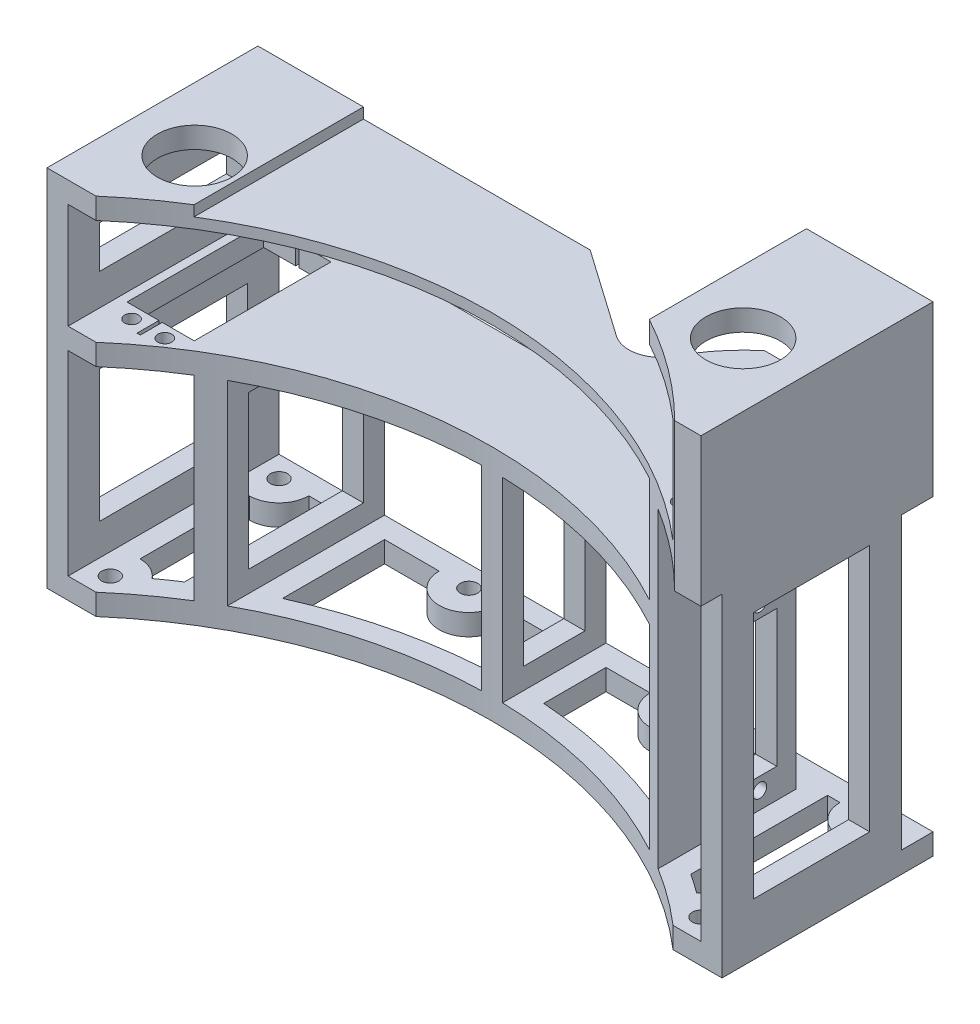
SolidWorks part; units mm, degrees
ref_plane "Front Plane" through (0, 0, 0) normal (0, 0, 1) x (1, 0, 0)
ref_plane "Top Plane" through (0, 0, 0) normal (0, 1, 0) x (1, 0, 0)
ref_plane "Right Plane" through (0, 0, 0) normal (1, 0, 0) x (0, 0, -1)
sketch "Sketch1" plane through (0, 0, 0) normal (0, 0, 1) x (1, 0, 0)
  line L0 (-101.6, 106.425) -> (101.6, 106.425)
  line L1 (-101.6, 0) -> (101.6, 0)
  line L2 (-101.6, 0) -> (-101.6, 106.425)
  line L4 (101.6, 0) -> (101.6, 106.425)
  point P5 (0, 0)
  dimension "D1" = 203.2
  dimension "D2" = 106.425
extrude "Boss-Extrude1" add sketch "Sketch1" along normal mid plane 63.5 contours L1 L4 L0 L2 | L0 region at (0, 53.2125, 0)
sketch "Sketch4" plane through (0, 0, -31.75) normal (0, 0, -1) x (-1, 0, 0)
  line L0 (-101.6, 0) -> (-101.6, 106.425) construction
  line L1 (101.6, 0) -> (101.6, 106.425) construction
  line L2 (-95.25, 103.25) -> (95.25, 103.25)
  line L3 (-95.25, 103.25) -> (-95.25, 71.5)
  line L4 (-95.25, 71.5) -> (95.25, 71.5)
  line L5 (95.25, 103.25) -> (95.25, 71.5)
  line L11 (-95.25, 65.15) -> (95.25, 65.15)
  line L12 (-95.25, 65.15) -> (-95.25, 6.35)
  line L13 (-95.25, 6.35) -> (95.25, 6.35)
  line L14 (95.25, 65.15) -> (95.25, 6.35)
  line L15 (101.6, 0) -> (-101.6, 0) construction
  dimension "D4" = 6.35
  dimension "D1" = 6.35
  dimension "D2" = 71.5
  dimension "D3" = 6.35
  dimension "D5" = 6.35
  dimension "D6" = 31.75
extrude "Cut-Extrude2" cut sketch "Sketch4" against normal through all
sketch "Sketch8" plane through (0, 0, 0) normal (0, 0, 1) x (1, 0, 0)
  line L0 (-95.25, 65.15) -> (95.25, 65.15) construction
  line L1 (-69.85, 65.15) -> (-63.5, 65.15)
  line L2 (-69.85, 65.15) -> (-69.85, 6.35)
  line L3 (-69.85, 6.35) -> (-63.5, 6.35)
  line L4 (-63.5, 65.15) -> (-63.5, 6.35)
  line L5 (95.25, 6.35) -> (-95.25, 6.35) construction
  line L6 (-95.25, 103.25) -> (95.25, 103.25) construction
  line L7 (63.5, 103.25) -> (69.85, 103.25)
  line L8 (63.5, 103.25) -> (63.5, 6.35)
  line L9 (63.5, 6.35) -> (69.85, 6.35)
  line L10 (69.85, 103.25) -> (69.85, 6.35)
  line L11 (95.25, 65.15) -> (95.25, 6.35) construction
  line L12 (-95.25, 6.35) -> (-95.25, 65.15) construction
  line L13 (-101.6, 0) -> (101.6, 0) construction
  line L14 (-3.175, 65.15) -> (3.175, 65.15)
  line L15 (-3.175, 65.15) -> (-3.175, 6.35)
  line L16 (-3.175, 6.35) -> (3.175, 6.35)
  line L17 (3.175, 65.15) -> (3.175, 6.35)
  point P24 (0, 0)
  point P25 (0, 6.35)
  dimension "D1" = 6.35
  dimension "D2" = 6.35
  dimension "D3" = 25.4
  dimension "D4" = 25.4
  dimension "D5" = 6.35
extrude "Boss-Extrude2" add sketch "Sketch8" along normal up to surface (31.75 mm away) from surface up to face at (0, 87.375, 31.75) starting at face at (0, 87.375, -31.75)
sketch "Sketch15" plane through (0, 103.25, 0) normal (0, -1, 0) x (1, 0, 0)
  line L4 (69.85, 31.75) -> (69.85, -31.75)
  line L5 (69.85, -31.75) -> (95.25, -31.75)
  line L6 (95.25, -31.75) -> (95.25, 31.75)
  line L7 (95.25, 31.75) -> (69.85, 31.75)
  line L8 (69.85, 31.75) -> (69.85, -31.75)
  line L9 (69.85, -31.75) -> (95.25, -31.75)
  line L10 (95.25, -31.75) -> (95.25, 31.75)
  line L11 (95.25, 31.75) -> (69.85, 31.75)
  dimension "D1" = 0
extrude "Boss-Extrude4" add sketch "Sketch15" along normal blind 3.175
sketch "Sketch2" plane through (0, 71.5, 0) normal (0, 1, 0) x (1, 0, 0)
  line L0 (-92.677, 24.55) -> (-72.423, -16.604) construction
  line L29 (-92.677, 24.55) -> (-83.05, 24.55)
  line L30 (-92.677, 24.55) -> (-92.677, -16.604)
  line L31 (-92.677, -16.604) -> (-83.05, -16.604)
  line L34 (-72.423, 24.55) -> (-72.423, -16.604)
  line L58 (69.85, 31.75) -> (69.85, -31.75)
  line L59 (69.85, -31.75) -> (95.25, -31.75)
  line L60 (95.25, -31.75) -> (95.25, 31.75)
  line L61 (95.25, 31.75) -> (69.85, 31.75)
  line L62 (69.85, 31.75) -> (69.85, -31.75)
  line L63 (69.85, -31.75) -> (95.25, -31.75)
  line L64 (95.25, -31.75) -> (95.25, 31.75)
  line L65 (95.25, 31.75) -> (69.85, 31.75)
  line L78 (-72.423, 24.55) -> (-92.677, -16.604) construction
  line L79 (-87.55, 28.273) -> (-77.55, -20.327) construction
  line L80 (-87.55, -20.327) -> (-77.55, 28.273) construction
  line L81 (-82.05, -16.604) -> (-72.423, -16.604)
  line L82 (-82.05, -16.604) -> (-82.05, -23.208)
  line L83 (-82.05, -23.208) -> (-83.05, -23.208)
  line L84 (-83.05, -16.604) -> (-83.05, -23.208)
  line L85 (-82.55, 3.973) -> (-13.3966, 3.973) construction
  line L86 (-82.05, 31.154) -> (-83.05, 31.154)
  line L87 (-82.05, 24.55) -> (-82.05, 31.154)
  line L88 (-83.05, 24.55) -> (-83.05, 31.154)
  line L89 (-82.05, 24.55) -> (-72.423, 24.55)
  line L90 (-101.6, -31.75) -> (101.6, -31.75) construction
  line L91 (-101.6, -31.75) -> (-101.6, 31.75) construction
  circle A12 centre (-87.55, -20.327) radius 2.1
  circle A13 centre (-77.55, -20.327) radius 2.1
  circle A14 centre (-87.55, 28.273) radius 2.1
  circle A15 centre (-77.55, 28.273) radius 2.1
  point P8 (-82.55, -23.208)
  point P17 (-82.55, 3.973)
  point P18 (-82.55, 3.973)
  point P27 (-82.55, -6.35)
  dimension "D3" = 48.6
  dimension "D4" = 4.2
  dimension "D2" = 10
  dimension "D5" = 41.154
  dimension "D6" = 20.254
  dimension "D7" = 1
  dimension "D8" = 6.604
  dimension "D9" = 30.9
  dimension "D10" = 25.4
  dimension "D11" = 0
  dimension "D12" = 19.05
extrude "Cut-Extrude3" cut sketch "Sketch2" against normal up to next
sketch "Sketch9" plane through (0, 106.425, 0) normal (0, 1, 0) x (1, 0, 0)
  line L0 (72.423, 24.55) -> (92.677, -16.604) construction
  line L1 (72.423, 24.55) -> (82.05, 24.55)
  line L2 (72.423, 24.55) -> (72.423, -16.604)
  line L3 (72.423, -16.604) -> (82.05, -16.604)
  line L4 (92.677, 24.55) -> (92.677, -16.604)
  line L5 (92.677, 24.55) -> (72.423, -16.604) construction
  line L6 (77.55, 28.273) -> (87.55, -20.327) construction
  line L7 (77.55, -20.327) -> (87.55, 28.273) construction
  line L8 (83.05, -16.604) -> (92.677, -16.604)
  line L9 (83.05, -16.604) -> (83.05, -23.208)
  line L10 (83.05, -23.208) -> (82.05, -23.208)
  line L11 (82.05, -16.604) -> (82.05, -23.208)
  line L12 (82.55, 3.973) -> (164.4034, 3.973) construction
  line L13 (83.05, 31.154) -> (82.05, 31.154)
  line L14 (83.05, 24.55) -> (83.05, 31.154)
  line L15 (82.05, 24.55) -> (82.05, 31.154)
  line L16 (83.05, 24.55) -> (92.677, 24.55)
  line L17 (101.6, -31.75) -> (101.6, 31.75) construction
  line L19 (-101.6, -31.75) -> (101.6, -31.75) construction
  circle A0 centre (77.55, -20.327) radius 2.1
  circle A1 centre (87.55, -20.327) radius 2.1
  circle A2 centre (77.55, 28.273) radius 2.1
  circle A3 centre (87.55, 28.273) radius 2.1
  point P8 (82.55, -23.208)
  point P17 (82.55, 3.973)
  point P18 (82.55, 3.973)
  point P27 (82.55, -6.35)
  dimension "D3" = 4.2
  dimension "D1" = 10
  dimension "D2" = 48.6
  dimension "D4" = 41.154
  dimension "D5" = 20.254
  dimension "D6" = 1
  dimension "D7" = 6.604
  dimension "D8" = 30.9
  dimension "D9" = 19.05
  dimension "D10" = 25.4
extrude "Cut-Extrude4" cut sketch "Sketch9" against normal up to next
sketch "Sketch12" plane through (0, 0, 0) normal (0, 1, 0) x (1, 0, 0)
  line L0 (-63.5, -31.75) -> (-63.5, 31.75) construction
  line L1 (-69.85, -31.75) -> (-95.25, -31.75) construction
  line L2 (-95.25, -31.75) -> (-95.25, 31.75) construction
  line L3 (-101.6, 31.75) -> (101.6, 31.75) construction
  circle A0 centre (-88.9, 25.4) radius 2.6
  circle A1 centre (-88.9, -25.4) radius 2.6
  circle A2 centre (-31.75, 25.4) radius 2.6
  dimension "D1" = 5.2
  dimension "D2" = 6.35
  dimension "D3" = 6.35
  dimension "D4" = 6.35
  dimension "D5" = 31.75
extrude "Cut-Extrude7" cut sketch "Sketch12" along normal up to surface (6.35 mm away) and the other way through all up to face at (-33.3375, 6.35, 0)
mirror "Mirror1" about plane through (0, 0, 0) normal (1, 0, 0) of "Cut-Extrude7"
sketch "Sketch16" plane through (0, 106.425, 0) normal (0, 1, 0) x (1, 0, 0)
  line L2 (-69.85, 31.75) -> (-101.6, 31.75)
  line L3 (-101.6, 31.75) -> (-101.6, -31.75)
  line L12 (-101.6, -31.75) -> (-69.85, -31.75)
  line L13 (-69.85, 31.75) -> (-69.85, -31.75)
  dimension "D1" = 31.75
extrude "Boss-Extrude5" add sketch "Sketch16" along normal blind 3.175
sketch "Sketch17" plane through (0, 109.6, 0) normal (0, 1, 0) x (1, 0, 0)
  line L0 (-101.6, -31.75) -> (-69.85, -31.75) construction
  line L1 (-101.6, 31.75) -> (-101.6, -31.75) construction
  circle A0 centre (-82.55, -6.35) radius 11.2395
  dimension "D3" = 22.479
  dimension "D1" = 25.4
  dimension "D2" = 19.05
extrude "Cut-Extrude8" cut sketch "Sketch17" against normal up to next
sketch "Sketch18" plane through (0, 106.425, 0) normal (0, 1, 0) x (1, 0, 0)
  line L5 (101.6, -31.75) -> (101.6, 31.75) construction
  line L6 (-69.85, -31.75) -> (101.6, -31.75) construction
  line L14 (101.6, -31.75) -> (101.6, 31.75)
  line L15 (101.6, 31.75) -> (95.25, 31.75)
  line L16 (95.25, -31.75) -> (95.25, 31.75)
  line L22 (95.25, -31.75) -> (82.55, -31.75)
  line L23 (101.6, -31.75) -> (101.6, -38.1)
  line L24 (101.6, -38.1) -> (82.55, -38.1)
  line L25 (82.55, -31.75) -> (82.55, -38.1)
  dimension "D4" = 6.35
  dimension "D5" = 19.05
extrude "Boss-Extrude6" add sketch "Sketch18" along normal blind 38.1 from surface starting at face at (87.55, 100.075, 18.227)
sketch "Sketch20" plane through (0, 138.175, 0) normal (0, 1, 0) x (1, 0, 0)
  line L1 (63.5, 31.75) -> (101.6, 31.75)
  line L2 (63.5, 31.75) -> (63.5, -38.1)
  line L3 (63.5, -38.1) -> (101.6, -38.1)
  line L4 (101.6, 31.75) -> (101.6, -38.1)
  line L6 (-69.85, -31.75) -> (82.55, -31.75) construction
  circle A0 centre (82.55, -6.35) radius 11.2395
  dimension "D2" = 19.05
  dimension "D1" = 22.479
  dimension "D4" = 38.1
  dimension "D3" = 25.4
extrude "Boss-Extrude7" add sketch "Sketch20" along normal blind 6.35
sketch "Sketch10" plane through (0, 106.425, 0) normal (0, 1, 0) x (1, 0, 0)
  circle A3 centre (0, -132.08) radius 131.1117 construction
  circle A4 centre (0, -132.08) radius 131.1117 construction
  circle A5 centre (0, -132.08) radius 132.6992
  dimension "D1" = 1.5875
extrude "Cut-Extrude5" cut sketch "Sketch10" against normal through all both and the other way through all
sketch "Sketch21" plane through (0, 106.425, 0) normal (0, 1, 0) x (1, 0, 0)
  line L5 (34.6759, 6.35) -> (-1.5991, 31.75)
  line L6 (-69.85, 31.75) -> (95.25, 31.75) construction
  line L7 (-1.5991, 31.75) -> (50.9018, 31.75)
  arc A1 (34.6759, 6.35) -> (50.9018, 31.75) centre (82.55, -6.35) cw
  dimension "D2" = 49.53
  dimension "D1" = 35
  dimension "D3" = 25.4
extrude "Cut-Extrude10" cut sketch "Sketch21" against normal up to surface (3.175 mm away) up to face at (-82.55, 103.25, 17.5895)
sketch "Sketch32" plane through (0, 6.35, 0) normal (0, 1, 0) x (1, 0, 0)
  line L8 (76.2, 25.4) -> (76.2, -15.769)
  line L9 (88.9, -25.1619) -> (88.9, 25.4)
  line L10 (88.9, 25.4) -> (76.2, 25.4)
  line L11 (76.2, 25.4) -> (76.2, -15.769)
  line L12 (88.9, -16.45) -> (88.9, 16.45)
  line L13 (79.95, 25.4) -> (76.2, 25.4)
  line L32 (-57.15, 25.4) -> (-57.15, -5.3181)
  line L33 (-9.525, 6.6426) -> (-9.525, 25.4)
  line L40 (-76.2, -15.769) -> (-76.2, 25.4)
  line L41 (-76.2, 25.4) -> (-88.9, 25.4)
  line L42 (-88.9, 25.4) -> (-88.9, -25.1619)
  line L43 (-76.2, -15.769) -> (-76.2, 25.4)
  line L44 (-76.2, 25.4) -> (-79.95, 25.4)
  line L45 (-88.9, 16.45) -> (-88.9, -16.45)
  line L48 (-9.525, 25.4) -> (-57.15, 25.4)
  line L49 (-57.15, 25.4) -> (-57.15, -5.3181)
  line L50 (-9.525, 6.6426) -> (-9.525, 25.4)
  line L67 (-9.525, 25.4) -> (-22.8, 25.4)
  line L68 (-40.7, 25.4) -> (-57.15, 25.4)
  line L69 (22.8, 25.4) -> (9.525, 25.4)
  line L71 (9.525, 25.4) -> (9.525, 6.6426)
  line L72 (57.15, -5.3181) -> (57.15, 25.4)
  line L73 (57.15, 25.4) -> (9.525, 25.4)
  line L74 (9.525, 25.4) -> (9.525, 6.6426)
  line L75 (57.15, -5.3181) -> (57.15, 25.4)
  line L76 (57.15, 25.4) -> (40.7, 25.4)
  circle A2 centre (88.9, 25.4) radius 8.95
  arc A3 (79.95, 25.4) -> (88.9, 16.45) centre (88.9, 25.4) ccw
  arc A8 (88.9, -25.1619) -> (76.2, -15.769) centre (0, -132.08) ccw
  circle A9 centre (88.9, -25.4) radius 8.95
  arc A10 (88.9, -16.45) -> (81.9575, -19.7516) centre (88.9, -25.4) ccw
  arc A11 (81.9575, -19.7516) -> (76.2, -15.769) centre (0, -132.08) ccw
  circle A13 centre (-31.75, 25.4) radius 8.95
  arc A22 (-76.2, -15.769) -> (-88.9, -25.1619) centre (0, -132.08) ccw
  arc A23 (-76.2, -15.769) -> (-81.9575, -19.7516) centre (0, -132.08) ccw
  arc A26 (-40.7, 25.4) -> (-22.8, 25.4) centre (-31.75, 25.4) ccw
  circle A27 centre (-88.9, 25.4) radius 8.95
  arc A28 (-88.9, 16.45) -> (-79.95, 25.4) centre (-88.9, 25.4) ccw
  circle A30 centre (-88.9, -25.4) radius 8.95
  arc A31 (-81.9575, -19.7516) -> (-88.9, -16.45) centre (-88.9, -25.4) ccw
  circle A33 centre (31.75, 25.4) radius 8.95
  arc A35 (22.8, 25.4) -> (40.7, 25.4) centre (31.75, 25.4) ccw
  arc A38 (-9.525, 6.6426) -> (-57.15, -5.3181) centre (0, -132.08) ccw
  arc A39 (-9.525, 6.6426) -> (-57.15, -5.3181) centre (0, -132.08) ccw
  arc A42 (57.15, -5.3181) -> (9.525, 6.6426) centre (0, -132.08) ccw
  arc A43 (57.15, -5.3181) -> (9.525, 6.6426) centre (0, -132.08) ccw
  dimension "D1" = 6.35
  dimension "D2" = 6.35
  dimension "D3" = 6.35
  dimension "D4" = 6.35
  dimension "D5" = 6.35
  dimension "D6" = 6.35
  dimension "D7" = 6.35
  dimension "D8" = 6.35
  dimension "D9" = 6.35
  dimension "D10" = 6.35
extrude "Cut-Extrude19" cut sketch "Sketch32" against normal up to next
sketch "Sketch23" plane through (0, 0, -31.75) normal (0, 0, -1) x (-1, 0, 0)
  line L1 (-101.6, 6.35) -> (-57.15, 6.35)
  line L2 (-101.6, 6.35) -> (-101.6, 93.725)
  line L3 (-101.6, 93.725) -> (-57.15, 93.725)
  line L4 (-57.15, 6.35) -> (-57.15, 93.725)
  line L7 (-63.5, 71.5) -> (95.25, 71.5) construction
  line L9 (-63.5, 65.15) -> (-63.5, 6.35) construction
  line L10 (-101.6, 0) -> (-101.6, 144.525) construction
  line L11 (-63.5, 6.35) -> (-3.175, 6.35) construction
  dimension "D1" = 6.35
  dimension "D2" = 22.225
extrude "Cut-Extrude11" cut sketch "Sketch23" against normal blind 9.525
sketch "Sketch24" plane through (63.5, 0, 0) normal (-1, 0, 0) x (0, 0, 1)
  line L0 (-16.477, 56.354) -> (3.777, 15.2) construction
  line L1 (-16.477, 56.354) -> (-6.85, 56.354)
  line L2 (-16.477, 56.354) -> (-16.477, 15.2)
  line L3 (-16.477, 15.2) -> (-6.85, 15.2)
  line L4 (3.777, 56.354) -> (3.777, 15.2)
  line L5 (3.777, 56.354) -> (-16.477, 15.2) construction
  line L6 (-11.35, 60.077) -> (-1.35, 11.477) construction
  line L7 (-11.35, 11.477) -> (-1.35, 60.077) construction
  line L8 (-5.85, 15.2) -> (3.777, 15.2)
  line L9 (-5.85, 15.2) -> (-5.85, 8.596)
  line L10 (-5.85, 8.596) -> (-6.85, 8.596)
  line L11 (-6.85, 15.2) -> (-6.85, 8.596)
  line L12 (-6.35, 35.777) -> (65.4757, 35.777) construction
  line L13 (-5.85, 62.958) -> (-6.85, 62.958)
  line L14 (-5.85, 56.354) -> (-5.85, 62.958)
  line L15 (-6.85, 56.354) -> (-6.85, 62.958)
  line L16 (-5.85, 56.354) -> (3.777, 56.354)
  line L17 (-22.225, 65.15) -> (-22.225, 6.35) construction
  line L18 (15.5603, 65.15) -> (-22.225, 65.15) construction
  circle A0 centre (-11.35, 11.477) radius 2.1
  circle A1 centre (-1.35, 11.477) radius 2.1
  circle A2 centre (-11.35, 60.077) radius 2.1
  circle A3 centre (-1.35, 60.077) radius 2.1
  point P8 (-6.35, 8.596)
  point P17 (-6.35, 35.777)
  point P18 (-6.35, 35.777)
  point P27 (-6.35, 46.1)
  dimension "D3" = 4.2
  dimension "D1" = 10
  dimension "D2" = 48.6
  dimension "D4" = 41.154
  dimension "D5" = 20.254
  dimension "D6" = 1
  dimension "D7" = 6.604
  dimension "D8" = 30.9
  dimension "D9" = 15.875
  dimension "D10" = 19.05
extrude "Cut-Extrude12" cut sketch "Sketch24" against normal up to next
sketch "Sketch26" plane through (95.25, 0, 0) normal (-1, 0, 0) x (0, 0, 1)
  line L12 (-12.7, 90.55) -> (-12.7, 15.875)
  line L13 (-12.7, 15.875) -> (22.225, 15.875)
  line L14 (22.225, 15.875) -> (22.225, 90.55)
  line L15 (22.225, 90.55) -> (-12.7, 90.55)
  line L16 (-12.7, 90.55) -> (-12.7, 15.875)
  line L17 (-12.7, 15.875) -> (22.225, 15.875)
  line L18 (22.225, 15.875) -> (22.225, 90.55)
  line L19 (22.225, 90.55) -> (-12.7, 90.55)
  dimension "D1" = 9.525
extrude "Cut-Extrude13" cut sketch "Sketch26" against normal up to next
sketch "Sketch27" plane through (63.5, 0, 0) normal (-1, 0, 0) x (0, 0, 1)
  line L12 (-15.875, 96.9) -> (-15.875, 77.85)
  line L13 (-15.875, 77.85) -> (9.2103, 77.85)
  line L14 (9.2103, 77.85) -> (9.2103, 96.9)
  line L15 (9.2103, 96.9) -> (-15.875, 96.9)
  line L16 (-15.875, 96.9) -> (-15.875, 77.85)
  line L17 (-15.875, 77.85) -> (9.2103, 77.85)
  line L18 (9.2103, 77.85) -> (9.2103, 96.9)
  line L19 (9.2103, 96.9) -> (-15.875, 96.9)
  dimension "D1" = 6.35
extrude "Cut-Extrude14" cut sketch "Sketch27" against normal up to next
sketch "Sketch28" plane through (3.175, 0, 0) normal (1, 0, 0) x (0, 0, -1)
  line L8 (25.4, 58.8) -> (6.9313, 58.8)
  line L9 (6.9313, 58.8) -> (6.9313, 12.7)
  line L10 (6.9313, 12.7) -> (25.4, 12.7)
  line L11 (25.4, 12.7) -> (25.4, 58.8)
  line L12 (25.4, 58.8) -> (6.9313, 58.8)
  line L13 (6.9313, 58.8) -> (6.9313, 12.7)
  line L14 (6.9313, 12.7) -> (25.4, 12.7)
  line L15 (25.4, 12.7) -> (25.4, 58.8)
  dimension "D1" = 6.35
extrude "Cut-Extrude15" cut sketch "Sketch28" against normal up to next
sketch "Sketch29" plane through (-63.5, 0, 0) normal (1, 0, 0) x (0, 0, -1)
  line L8 (25.4, 58.8) -> (-9.2103, 58.8)
  line L9 (-9.2103, 58.8) -> (-9.2103, 12.7)
  line L10 (-9.2103, 12.7) -> (25.4, 12.7)
  line L11 (25.4, 12.7) -> (25.4, 58.8)
  line L12 (25.4, 58.8) -> (-9.2103, 58.8)
  line L13 (-9.2103, 58.8) -> (-9.2103, 12.7)
  line L14 (-9.2103, 12.7) -> (25.4, 12.7)
  line L15 (25.4, 12.7) -> (25.4, 58.8)
  dimension "D1" = 6.35
extrude "Cut-Extrude16" cut sketch "Sketch29" against normal up to next
sketch "Sketch30" plane through (-95.25, 0, 0) normal (1, 0, 0) x (0, 0, -1)
  line L8 (22.225, 15.875) -> (22.225, 55.625)
  line L9 (22.225, 55.625) -> (-22.225, 55.625)
  line L10 (-22.225, 55.625) -> (-22.225, 15.875)
  line L11 (-22.225, 15.875) -> (22.225, 15.875)
  line L12 (22.225, 15.875) -> (22.225, 55.625)
  line L13 (22.225, 55.625) -> (-22.225, 55.625)
  line L14 (-22.225, 55.625) -> (-22.225, 15.875)
  line L15 (-22.225, 15.875) -> (22.225, 15.875)
  dimension "D1" = 9.525
extrude "Cut-Extrude17" cut sketch "Sketch30" against normal up to next
sketch "Sketch31" plane through (-95.25, 0, 0) normal (1, 0, 0) x (0, 0, -1)
  line L4 (22.225, 81.025) -> (22.225, 93.725)
  line L6 (22.225, 81.025) -> (22.225, 93.725)
  line L9 (22.225, 93.725) -> (-22.225, 93.725)
  line L10 (-22.225, 93.725) -> (-22.225, 81.025)
  line L11 (-22.225, 81.025) -> (22.225, 81.025)
  line L13 (22.225, 93.725) -> (-22.225, 93.725)
  line L14 (-22.225, 93.725) -> (-22.225, 81.025)
  line L15 (-22.225, 81.025) -> (22.225, 81.025)
  dimension "D1" = 9.525
extrude "Cut-Extrude18" cut sketch "Sketch31" against normal up to next
fillet "Fillet1" radius 9.525 1 edges at (34.6759, 104.8375, -6.35)
equation "\"tightTol\" = 0.005in"
equation "\"normTol\" = 0.01in"
equation "\"looseTol\" = 0.02in"
equation "\"D1@Sketch12\"=5.2mm"
equation "\"D2@Sketch1\"=8mm+0.5+3.25+0.125"
equation "\"D2@Sketch4\"=8mm+0.25+2.25"
equation "\"D3@Sketch17\" = 7 / 8 + \"normTol\""
equation "\"D1@Sketch20\"=7/8+\"normTol\""
